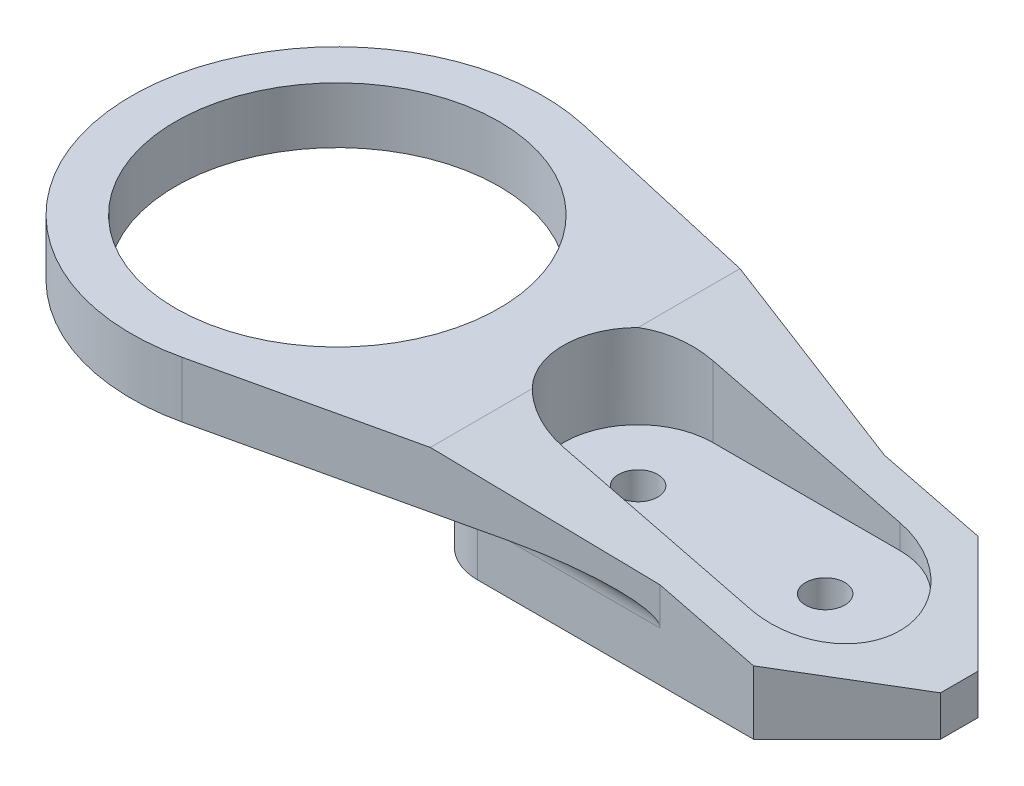
SolidWorks part; units mm, degrees
material "Tough 2000"
ref_plane "Front Plane" through (0, 0, 0) normal (0, 0, 1) x (1, 0, 0)
ref_plane "Top Plane" through (0, 0, 0) normal (0, 1, 0) x (1, 0, 0)
ref_plane "Right Plane" through (0, 0, 0) normal (1, 0, 0) x (0, 0, -1)
sketch "Sketch1" plane through (0, 0, 0) normal (0, 0, 1) x (1, 0, 0)
  line L0 (0, 0) -> (0, 7.15)
  line L1 (0, 7.15) -> (25, 7.15)
  line L2 (25, 7.15) -> (25, 0)
  line L3 (25, 0) -> (0, 0)
extrude "Boss-Extrude1" add sketch "Sketch1" along normal blind 12
sketch "Sketch2" plane through (0, 7.15, 0) normal (0, 1, 0) x (1, 0, 0)
  line L0 (0, -6) -> (-8.25, -6) construction
  line L1 (0, -12) -> (0, 0) construction
  line L3 (25, 0) -> (0, 0) construction
  line L5 (25, -12) -> (0, -12) construction
  line L8 (15, -6) -> (15, 0)
  line L11 (15, 0) -> (-5.8049, 4.7375)
  line L12 (15, -6) -> (15, -12)
  line L13 (15, -12) -> (-5.8049, -16.7375)
  arc A6 (-5.8049, 4.7375) -> (-5.8049, -16.7375) centre (-8.25, -6) ccw
  line M4 (25, 0) -> (0, 0)
  line M5 (0, 0) -> (0, -12)
  line M6 (0, -12) -> (25, -12)
extrude "Boss-Extrude2" add sketch "Sketch2" against normal blind 3 contours M6 M5 M4 region at (-7.1054, 7.15, 6)
sketch "Sketch3" plane through (0, 4.15, 0) normal (0, -1, 0) x (1, 0, 0)
  line L0 (-8.25, 6) -> (2.25, 6) construction
  line L1 (2.25, 6) -> (2.25, 12)
  line L2 (0, 12) -> (25, 12) construction
  line L3 (2.25, 12) -> (0, 12)
  line L4 (0, 12) -> (0, 0)
  line L5 (0, 0) -> (2.25, 0)
  line L6 (15, 0) -> (0, 0) construction
  line L7 (2.25, 0) -> (2.25, 6)
  circle A0 centre (-8.25, 6) radius 11.0124 construction
extrude "Cut-Extrude1" cut sketch "Sketch3" along normal blind 21
sketch "Sketch4" plane through (0, 4.15, 0) normal (0, -1, 0) x (1, 0, 0)
  circle A2 centre (-8.25, 6) radius 8.65
extrude "Cut-Extrude2" cut sketch "Sketch4" against normal blind 10
chamfer "Chamfer1" distance 5 distance2 20 1 edges at (25, 7.15, 6) first distance on face at (25, 3.575, 6)
chamfer "Chamfer2" distance 5 angle 45 2 edges at (25, 1.075, 12) (25, 1.075, 0)
sketch "Sketch6" plane through (0, 7.15, 0) normal (0, 1, 0) x (1, 0, 0)
  line L0 (-0.0037, -6) -> (7.8299, -6) construction
  line L1 (7.8299, -6) -> (17.8299, -6) construction
  circle A0 centre (-8.5537, -6) radius 8.55 construction
  circle A1 centre (7.8299, -6) radius 1.05
  circle A2 centre (17.8299, -6) radius 1.05
  dimension "D1" = 10
extrude "Cut-Extrude3" cut sketch "Sketch6" against normal blind 10
sketch "Sketch7" plane through (0, 7.15, 0) normal (0, 1, 0) x (1, 0, 0)
  line L0 (7.8299, -2) -> (17.8299, -2)
  line L1 (17.8299, -10) -> (7.8299, -10)
  arc A0 (7.8299, -2) -> (7.8299, -10) centre (7.8299, -6) ccw
  arc A1 (17.8299, -10) -> (17.8299, -2) centre (17.8299, -6) ccw
extrude "Cut-Extrude4" cut sketch "Sketch7" against normal blind 4.5
fillet "Fillet1" radius 3 2 edges at (2.25, 2.075, 12) (2.25, 2.075, 0)
fillet "Fillet2" radius 1.5 5 edges at (10.125, 4.15, 12) (3.1287, 4.15, 11.1213) (2.25, 4.15, 6) (3.1287, 4.15, 0.8787) (10.125, 4.15, 0)
